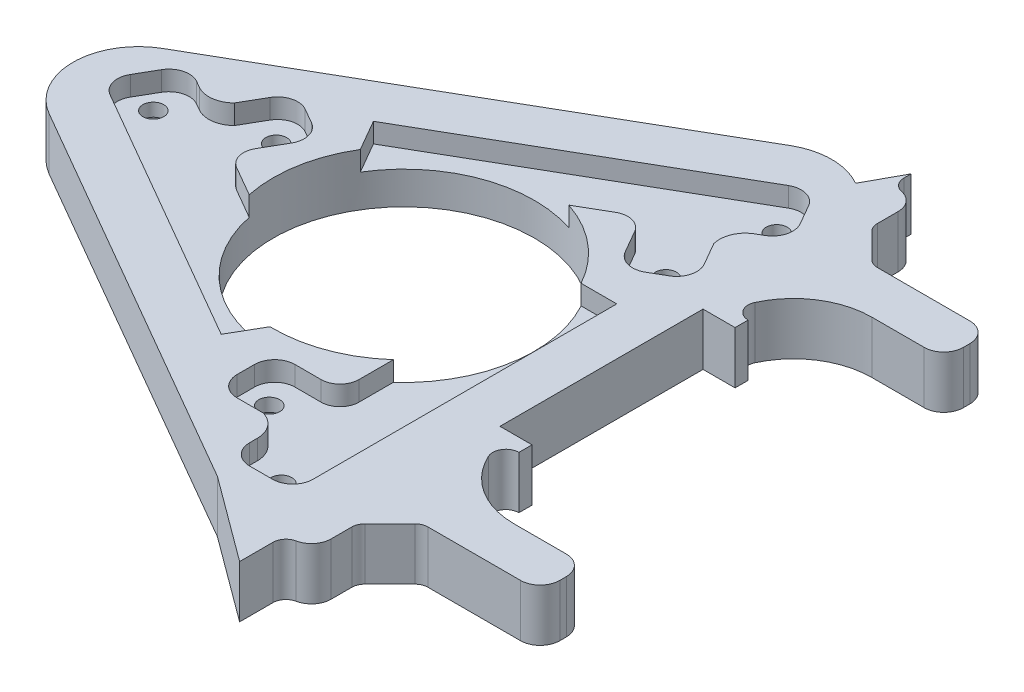
SolidWorks part; units mm, degrees
ref_plane "Plan de face" through (0, 0, 0) normal (0, 0, 1) x (1, 0, 0)
ref_plane "Plan de dessus" through (0, 0, 0) normal (0, 1, 0) x (1, 0, 0)
ref_plane "Plan de droite" through (0, 0, 0) normal (1, 0, 0) x (0, 0, -1)
sketch "Esquisse1" plane through (0, 0, 0) normal (0, 1, 0) x (1, 0, 0)
  line L7 (14.4338, 0) -> (-7.2169, 12.5) construction
  line L8 (-7.2169, 12.5) -> (-7.2169, -12.5) construction
  line L9 (-7.2169, -12.5) -> (14.4338, 0) construction
  circle A0 centre (0, 0) radius 7.2169 construction
  circle A1 centre (-7.2169, -12.5) radius 2 construction
  circle A2 centre (-7.2169, 12.5) radius 2 construction
  circle A3 centre (14.4338, 0) radius 2 construction
  dimension "D2" = 4
  dimension "D3" = 4
  dimension "D4" = 4
  dimension "D1" = 25
sketch "Esquisse4" plane through (0, 0, 0) normal (0, 1, 0) x (1, 0, 0)
  line L0 (14.8238, 7.28) -> (16.4238, 7.28) construction
  line L1 (16.4238, 7.28) -> (16.4238, -22.72) construction
  line L2 (16.4238, -22.72) -> (14.8238, -22.72) construction
  line L3 (14.8238, -22.72) -> (14.8238, 7.28) construction
  line L7 (-1.1072, -16.4777) -> (-27.088, -1.4777) construction
  line L8 (-27.088, -1.4777) -> (-27.888, -2.8634) construction
  line L9 (-7.2169, 12.5) -> (-7.2169, -12.5) construction
  line L10 (-13.7165, 9.1977) -> (-14.5165, 10.5834) construction
  line L11 (-14.5165, 10.5834) -> (11.4642, 25.5834) construction
  line L12 (11.4642, 25.5834) -> (12.2642, 24.1977) construction
  line L13 (12.2642, 24.1977) -> (-13.7165, 9.1977) construction
  line L14 (-7.2169, -12.5) -> (14.4338, 0) construction
  line L15 (-27.888, -2.8634) -> (-1.9072, -17.8634) construction
  line L16 (-1.9072, -17.8634) -> (-1.1072, -16.4777) construction
  dimension "D2" = 1.6
  dimension "D3" = 30
  dimension "D4" = 7.28
  dimension "D5" = 0.39
  dimension "D6" = 60
  dimension "D7" = 0.39
  dimension "D8" = 1.6
  dimension "D9" = 1.6
  dimension "D10" = 0.39
  dimension "D11" = 7.28
  dimension "D12" = 30
  dimension "D13" = 1.6
  dimension "D14" = 7.28
  dimension "D15" = 30
  dimension "D16" = 1.6
  dimension "D17" = 60
sketch "Esquisse5" plane through (0, 0, 0) normal (0, 1, 0) x (1, 0, 0)
  line L0 (-7.2169, 12.5) -> (-7.2169, -12.5) construction
  line L1 (30.3109, -52.5) -> (30.3109, 52.5)
  line L2 (30.3109, 52.5) -> (-60.6218, 0)
  line L3 (-60.6218, 0) -> (30.3109, -52.5)
  circle A1 centre (0, 0) radius 20
  circle A2 centre (0, 0) radius 30.3109 construction
  dimension "D1" = 105
  dimension "D2" = 40
extrude "Boss.-Extru.1" add sketch "Esquisse5" along normal blind 8
ref_axis "Axe1" through (0, 130.0156, 0) along (0, -1, 0)
sketch "Esquisse8" plane through (0, 8, 0) normal (0, 1, 0) x (1, 0, 0)
  line L32 (-32.788, 6.8938) -> (-30.788, 10.3579) construction
  line L33 (-44.5284, 2.7025) -> (-42.7784, 5.7336) construction
  line L36 (-38.6803, 6.8317) -> (-37.6693, 6.2479) construction
  line L37 (-24.1899, -1.5344) -> (1.4928, -16.3623) construction
  line L40 (1.4928, -16.3623) -> (-3.2572, -24.5895) construction
  line L41 (-13.1835, -18.8586) -> (3.6691, -28.5884) construction
  line L52 (-3.2572, -24.5895) -> (1.4928, -16.3623) construction
  line L53 (-3.2572, -24.5895) -> (-43.4303, -1.3956) construction
  line L54 (-26.6899, 11.456) -> (-24.3861, 10.1259) construction
  line L55 (-23.288, 6.0278) -> (-25.288, 2.5637) construction
  line L56 (-25.288, 2.5637) -> (-23.288, 6.0278) construction
  line L82 (-32.868, 6.9552) -> (-30.8746, 10.4079)
  line L83 (-26.6399, 11.5426) -> (-24.3361, 10.2125)
  line L84 (-23.2014, 5.9778) -> (-25.2014, 2.5137)
  line L85 (-24.1399, -1.4478) -> (1.6294, -16.3257)
  line L86 (1.6294, -16.3257) -> (-3.2206, -24.7261)
  line L87 (-3.2206, -24.7261) -> (-43.4803, -1.4822)
  line L88 (-44.615, 2.7525) -> (-42.865, 5.7836)
  line L89 (-38.6303, 6.9183) -> (-37.6193, 6.3345)
  line L112 (22.4574, 24.9869) -> (24.4508, 21.5342)
  line L113 (23.3161, 17.2995) -> (21.0123, 15.9694)
  line L114 (16.7776, 17.1041) -> (14.7776, 20.5682)
  line L115 (10.8161, 21.6297) -> (-14.9531, 6.7517)
  line L116 (-14.9531, 6.7517) -> (-19.8031, 15.1522)
  line L117 (-19.8031, 15.1522) -> (20.4565, 38.3961)
  line L118 (24.6912, 37.2614) -> (26.4412, 34.2304)
  line L119 (25.3065, 29.9957) -> (24.2955, 29.412)
  line L128 (22.3642, 24.9483) -> (24.3642, 21.4842) construction
  line L129 (24.6046, 37.2114) -> (26.3546, 34.1804) construction
  line L130 (25.2565, 30.0823) -> (24.2455, 29.4986) construction
  line L131 (10.7661, 21.7163) -> (-14.9165, 6.8883) construction
  line L132 (-14.9165, 6.8883) -> (-19.6665, 15.1156) construction
  line L133 (-19.6665, 15.1156) -> (20.5065, 38.3095) construction
  line L134 (23.2661, 17.3861) -> (20.9623, 16.056) construction
  line L135 (16.8642, 17.1541) -> (14.8642, 20.6182) construction
  line L136 (10.4106, -31.9421) -> (6.4238, -31.9421)
  line L137 (3.3238, -28.8421) -> (3.3238, -26.1819)
  line L138 (6.4238, -23.0819) -> (10.4238, -23.0819)
  line L139 (13.3238, -20.1819) -> (13.3238, 9.5739)
  line L140 (13.3238, 9.5739) -> (23.0238, 9.5739)
  line L141 (23.0238, 9.5739) -> (23.0238, -36.9139)
  line L142 (19.9238, -40.0139) -> (16.4238, -40.0139)
  line L143 (13.3238, -36.9139) -> (13.3238, -35.7465)
  line L144 (10.4238, -31.8421) -> (6.4238, -31.8421) construction
  line L145 (19.9238, -39.9139) -> (16.4238, -39.9139) construction
  line L146 (13.4238, -36.9139) -> (13.4238, -35.7465) construction
  line L147 (13.4238, -20.1819) -> (13.4238, 9.4739) construction
  line L148 (13.4238, 9.4739) -> (22.9238, 9.4739) construction
  line L149 (22.9238, 9.4739) -> (22.9238, -36.9139) construction
  line L150 (3.4238, -28.8421) -> (3.4238, -26.1819) construction
  line L151 (6.4238, -23.1819) -> (10.4238, -23.1819) construction
  arc A8 (-43.4303, -1.3956) -> (-44.5284, 2.7025) centre (-41.9303, 1.2025) cw construction
  arc A10 (-42.7784, 5.7336) -> (-38.6803, 6.8317) centre (-40.1803, 4.2336) cw construction
  arc A11 (-37.6693, 6.2479) -> (-32.788, 6.8938) centre (-35.6489, 9.7473) ccw construction
  arc A12 (-25.288, 2.5637) -> (-25.6873, 1.1888) centre (-22.6899, 1.0637) ccw construction
  arc A13 (-30.788, 10.3579) -> (-26.6899, 11.456) centre (-28.1899, 8.8579) cw construction
  arc A14 (-24.3861, 10.1259) -> (-23.288, 6.0278) centre (-25.8861, 7.5278) cw construction
  arc A15 (-25.288, 2.5637) -> (-24.1899, -1.5344) centre (-22.6899, 1.0637) ccw construction
  arc A28 (-30.8746, 10.4079) -> (-26.6399, 11.5426) centre (-28.1899, 8.8579) cw
  arc A29 (-24.3361, 10.2125) -> (-23.2014, 5.9778) centre (-25.8861, 7.5278) cw
  arc A30 (-25.2014, 2.5137) -> (-24.1399, -1.4478) centre (-22.6899, 1.0637) ccw
  arc A31 (-43.4803, -1.4822) -> (-44.615, 2.7525) centre (-41.9303, 1.2025) cw
  arc A32 (-42.865, 5.7836) -> (-38.6303, 6.9183) centre (-40.1803, 4.2336) cw
  arc A33 (-37.6193, 6.3345) -> (-32.868, 6.9552) centre (-35.6489, 9.7473) ccw
  arc A52 (24.4508, 21.5342) -> (23.3161, 17.2995) centre (21.7661, 19.9842) cw
  arc A53 (21.0123, 15.9694) -> (16.7776, 17.1041) centre (19.4623, 18.6541) cw
  arc A54 (14.7776, 20.5682) -> (10.8161, 21.6297) centre (12.2661, 19.1182) ccw
  arc A55 (20.4565, 38.3961) -> (24.6912, 37.2614) centre (22.0065, 35.7114) cw
  arc A56 (26.4412, 34.2304) -> (25.3065, 29.9957) centre (23.7565, 32.6804) cw
  arc A57 (24.2955, 29.412) -> (22.4574, 24.9869) centre (26.2658, 25.9992) ccw
  arc A64 (20.5065, 38.3095) -> (24.6046, 37.2114) centre (22.0065, 35.7114) cw construction
  arc A65 (26.3546, 34.1804) -> (25.2565, 30.0823) centre (23.7565, 32.6804) cw construction
  arc A66 (24.2455, 29.4986) -> (22.3642, 24.9483) centre (26.2658, 25.9992) ccw construction
  arc A67 (24.3642, 21.4842) -> (23.2661, 17.3861) centre (21.7661, 19.9842) cw construction
  arc A68 (20.9623, 16.056) -> (16.8642, 17.1541) centre (19.4623, 18.6541) cw construction
  arc A69 (14.8642, 20.6182) -> (10.7661, 21.7163) centre (12.2661, 19.1182) ccw construction
  arc A70 (6.4238, -31.9421) -> (3.3238, -28.8421) centre (6.4238, -28.8421) cw
  arc A71 (3.3238, -26.1819) -> (6.4238, -23.0819) centre (6.4238, -26.1819) cw
  arc A72 (10.4238, -23.0819) -> (13.3238, -20.1819) centre (10.4238, -20.1819) ccw
  arc A73 (23.0238, -36.9139) -> (19.9238, -40.0139) centre (19.9238, -36.9139) cw
  arc A74 (16.4238, -40.0139) -> (13.3238, -36.9139) centre (16.4238, -36.9139) cw
  arc A75 (13.3238, -35.7465) -> (10.4106, -31.9421) centre (9.3831, -35.7465) ccw
  arc A76 (22.9238, -36.9139) -> (19.9238, -39.9139) centre (19.9238, -36.9139) cw construction
  arc A77 (16.4238, -39.9139) -> (13.4238, -36.9139) centre (16.4238, -36.9139) cw construction
  arc A78 (13.4238, -35.7465) -> (10.4238, -31.8421) centre (9.3831, -35.7465) ccw construction
  arc A79 (6.4238, -31.8421) -> (3.4238, -28.8421) centre (6.4238, -28.8421) cw construction
  arc A80 (3.4238, -26.1819) -> (6.4238, -23.1819) centre (6.4238, -26.1819) cw construction
  arc A81 (10.4238, -23.1819) -> (13.4238, -20.1819) centre (10.4238, -20.1819) ccw construction
  point P31 (-0.75, -1.299)
  point P35 (0.75, -1.299)
  point P108 (1.4434, -0.8333)
  point P148 (0, 1.6667)
  point P150 (-1.4434, -0.8333)
  point P151 (0, 0)
  dimension "D1" = 0.1
extrude "Enlèv. mat.-Extru.1" cut sketch "Esquisse8" against normal blind 3
hole_wizard "Dégagement M32" positions "Esquisse13" profile "Esquisse14" hole size "M3" standard "Ansi Metric" end condition through all
sketch "Esquisse13" plane through (0, 5, 0) normal (0, 1, 0) x (1, 0, 0)
  line L0 (22.9238, -36.9139) -> (13.4238, -36.9139) construction
  point P9 (-41.0553, 2.718)
  point P12 (-27.288, 7.7599)
  point P15 (20.3642, 19.7522)
  point P18 (22.8815, 34.1959)
  point P21 (6.9238, -27.512)
  point P27 (18.1738, -36.9139)
sketch "Esquisse14" plane through (-41.0553, 5, -2.718) normal (1, 0, 0) x (0, 0, 1)
  line L0 (0, 0) -> (0, 5)
  line L1 (0, 5) -> (1.6, 5)
  line L2 (1.6, 5) -> (1.6, 0)
  line L5 (1.6, 0) -> (0, 0)
  line L11 (0, -6.35) -> (0, 107.95) construction
  dimension "Diamètre du perçage jusqu'au prochain" = 3.2
  dimension "Profondeur du perçage jusqu'au prochain" = 5
sketch "Esquisse15" plane through (0, 0, 0) normal (0, -1, 0) x (-1, 0, 0)
  line L0 (-3.4238, -27.512) -> (-10.4238, -27.512) construction
  line L1 (40.2905, -0.4234) -> (43.3934, 0.485)
  line L2 (43.3934, 0.485) -> (44.1582, 3.6264)
  line L3 (44.1582, 3.6264) -> (41.8201, 5.8594)
  line L4 (41.8201, 5.8594) -> (38.7171, 4.9511)
  line L5 (38.7171, 4.9511) -> (37.9523, 1.8097)
  line L6 (37.9523, 1.8097) -> (40.2905, -0.4234)
  line L7 (-25.9002, 35.3539) -> (-25.3937, 32.1607)
  line L8 (-25.3937, 32.1607) -> (-22.3751, 31.0026)
  line L9 (-22.3751, 31.0026) -> (-19.8629, 33.0379)
  line L10 (-19.8629, 33.0379) -> (-20.3693, 36.2311)
  line L11 (-20.3693, 36.2311) -> (-23.388, 37.3892)
  line L12 (-23.388, 37.3892) -> (-25.9002, 35.3539)
  line L13 (-21.2639, -37.865) -> (-18.8951, -40.0656)
  line L14 (-18.8951, -40.0656) -> (-15.805, -39.1145)
  line L15 (-15.805, -39.1145) -> (-15.0837, -35.9628)
  line L16 (-15.0837, -35.9628) -> (-17.4524, -33.7623)
  line L17 (-17.4524, -33.7623) -> (-20.5425, -34.7134)
  line L18 (-20.5425, -34.7134) -> (-21.2639, -37.865)
  line L19 (-3.6906, -27.512) -> (-5.3072, -24.712)
  line L20 (-5.3072, -24.712) -> (-8.5403, -24.712)
  line L21 (-8.5403, -24.712) -> (-10.1569, -27.512)
  line L22 (-10.1569, -27.512) -> (-8.5403, -30.312)
  line L23 (-8.5403, -30.312) -> (-5.3072, -30.312)
  line L24 (-5.3072, -30.312) -> (-3.6906, -27.512)
  line L26 (29.9325, 5.8997) -> (30.2211, 9.12)
  line L27 (30.2211, 9.12) -> (27.5766, 10.9801)
  line L28 (27.5766, 10.9801) -> (24.6435, 9.62)
  line L29 (24.6435, 9.62) -> (24.3548, 6.3997)
  line L30 (24.3548, 6.3997) -> (26.9993, 4.5396)
  line L31 (26.9993, 4.5396) -> (29.9325, 5.8997)
  line L32 (-17.7197, 21.6123) -> (-20.6529, 22.9724)
  line L33 (-20.6529, 22.9724) -> (-23.2974, 21.1123)
  line L34 (-23.2974, 21.1123) -> (-23.0087, 17.892)
  line L35 (-23.0087, 17.892) -> (-20.0755, 16.5319)
  line L36 (-20.0755, 16.5319) -> (-17.4311, 18.392)
  line L37 (-17.4311, 18.392) -> (-17.7197, 21.6123)
  circle A0 centre (41.0553, 2.718) radius 2.8 construction
  circle A1 centre (-22.8815, 34.1959) radius 2.8 construction
  circle A2 centre (-18.1738, -36.9139) radius 2.8 construction
  circle A3 centre (-6.9238, -27.512) radius 2.8 construction
  circle A4 centre (27.288, 7.7599) radius 2.8 construction
  circle A5 centre (-20.3642, 19.7522) radius 2.8 construction
  point P50 (-6.9238, -24.712)
  point P59 (25.6771, 5.4697)
  dimension "D1" = 5.6
  dimension "D2" = 5.6
  dimension "D3" = 5.6
  dimension "D4" = 5.6
  dimension "D5" = 5.6
  dimension "D6" = 5.6
extrude "Enlèv. mat.-Extru.3" cut sketch "Esquisse15" against normal blind 3
fillet "Congé1" radius 10 3 edges at (30.3109, 4, -52.5) (30.3109, 4, 52.5) (-60.6218, 4, 0)
sketch "Esquisse18" plane through (0, 0, 0) normal (0, 1, 0) x (-1, 0, 0)
  line L7 (-88.6339, -70.13) -> (-88.6339, 68.2127) construction
  line L11 (0, 0) -> (-50.1791, 0) construction
  line L42 (-28.3109, -49.3365) -> (-25.3109, -43.8397)
  line L43 (-28.3109, -49.3365) -> (-28.3109, -48.2355)
  line L44 (-32.3109, -43.3365) -> (-32.3109, -40.165)
  line L45 (-32.8967, -38.7508) -> (-36.7251, -34.9223)
  line L46 (-38.1393, -34.3365) -> (-52.3109, -34.3365)
  line L47 (-52.3109, -27.3365) -> (-44.3109, -27.3365)
  line L48 (-55.3109, -31.3365) -> (-55.3109, -30.3365)
  line L49 (-30.3109, -15.489) -> (-30.3109, -35.1754)
  line L50 (-35.2138, -17.489) -> (-35.2138, -15.489)
  line L51 (-35.2138, -15.489) -> (-30.3109, -15.489)
  line L52 (-28.3109, 53.4392) -> (-15.3109, 43.8397)
  line L53 (-28.3109, 53.4392) -> (-28.3109, 48.3382)
  line L54 (-32.3109, 43.4392) -> (-32.3109, 40.2676)
  line L55 (-32.8967, 38.8534) -> (-36.7251, 35.025)
  line L56 (-38.1393, 34.4392) -> (-52.3109, 34.4392)
  line L57 (-55.3109, 31.4392) -> (-55.3109, 30.4392)
  line L58 (-52.3109, 27.4392) -> (-44.3109, 27.4392)
  line L59 (-35.2138, 17.5917) -> (-35.2138, 15.5917)
  line L60 (-35.2138, 15.5917) -> (-30.3109, 15.5917)
  line L61 (-30.3109, 15.5917) -> (-30.3109, 35.1795)
  arc A0 (-15.3109, 43.8397) -> (-30.3109, 35.1795) centre (-20.3109, 35.1795) ccw construction
  arc A37 (-28.3109, -48.2355) -> (-29.9109, -46.2759) centre (-30.3109, -48.2355) ccw
  arc A38 (-29.9109, -46.2759) -> (-32.3109, -43.3365) centre (-29.3109, -43.3365) cw
  arc A39 (-52.3109, -34.3365) -> (-55.3109, -31.3365) centre (-52.3109, -31.3365) cw
  arc A40 (-52.3109, -27.3365) -> (-55.3109, -30.3365) centre (-52.3109, -30.3365) ccw
  arc A41 (-44.3109, -27.3365) -> (-33.3944, -20.3195) centre (-44.3109, -15.3365) ccw
  arc A42 (-30.3109, -35.1754) -> (-25.3109, -43.8397) centre (-20.3109, -35.1795) ccw
  arc A43 (-33.3944, -20.3195) -> (-35.2138, -17.489) centre (-35.2138, -19.489) ccw
  arc A44 (-28.3109, 48.3382) -> (-29.9109, 46.3786) centre (-30.3109, 48.3382) cw
  arc A45 (-29.9109, 46.3786) -> (-32.3109, 43.4392) centre (-29.3109, 43.4392) ccw
  arc A46 (-32.3109, 40.2676) -> (-32.8967, 38.8534) centre (-34.3109, 40.2676) cw
  arc A47 (-36.7251, 35.025) -> (-38.1393, 34.4392) centre (-38.1393, 36.4392) cw
  arc A48 (-52.3109, 34.4392) -> (-55.3109, 31.4392) centre (-52.3109, 31.4392) ccw
  arc A49 (-55.3109, 30.4392) -> (-52.3109, 27.4392) centre (-52.3109, 30.4392) ccw
  arc A50 (-44.3109, 27.4392) -> (-33.3944, 20.4222) centre (-44.3109, 15.4392) cw
  arc A51 (-33.3944, 20.4222) -> (-35.2138, 17.5917) centre (-35.2138, 19.5917) cw
  arc A52 (-30.3109, 35.1795) -> (-15.3109, 43.8397) centre (-20.3109, 35.1795) cw
  arc A53 (-32.3109, -40.165) -> (-32.8967, -38.7508) centre (-34.3109, -40.165) ccw
  arc A54 (-36.7251, -34.9223) -> (-38.1393, -34.3365) centre (-38.1393, -36.3365) ccw
  arc A55 (-30.3109, -35.1795) -> (-15.3109, -43.8397) centre (-20.3109, -35.1795) ccw construction
  arc A56 (-30.3109, -35.1795) -> (-15.3109, -43.8397) centre (-20.3109, -35.1795) ccw construction
  point P5 (-24.6856, -44.3418)
  point P12 (-25.3109, -43.8397)
  point P49 (0, 0)
  dimension "D1" = 0
  dimension "D2" = 0
extrude "Boss.-Extru.3" add sketch "Esquisse18" along direction (0, 1, 0) on the side of the normal up to surface (8 mm away) up to face at (0, 8, 0)
